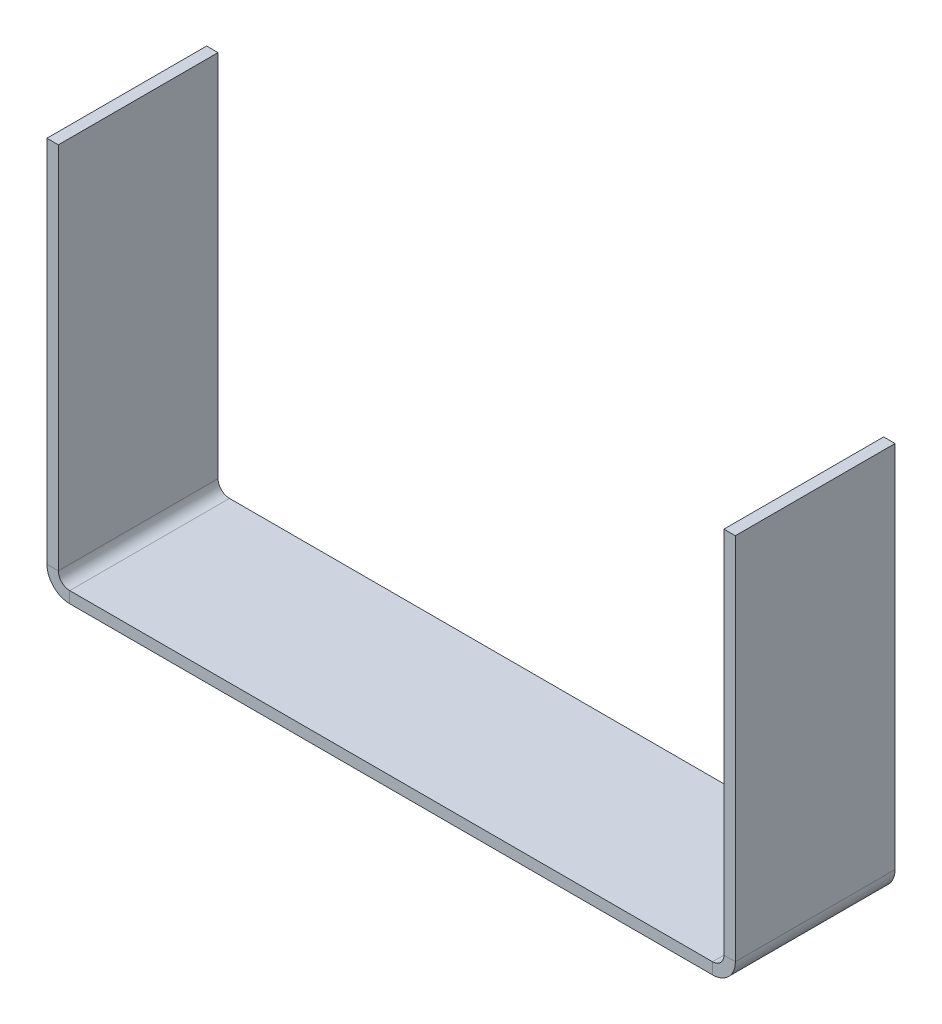
SolidWorks part; units mm, degrees
note: The reader was unsure of these and kept them because the rebuilt part matched: thickness of "Base-Flange1", "Sheet-Metal34"; bend radius of "Base-Flange1", "BaseBend1", "BaseBend2".
material "Tole inox 304 - Z7CN18.09"
ref_plane "Plan de face" through (0, 0, 0) normal (0, 0, 1) x (1, 0, 0)
ref_plane "Plan de dessus" through (0, 0, 0) normal (0, 1, 0) x (1, 0, 0)
ref_plane "Plan de droite" through (0, 0, 0) normal (1, 0, 0) x (0, 0, -1)
sketch "Sketch1" plane through (0, 0, 0) normal (0, 0, 1) x (1, 0, 0)
  line L0 (-87.5, 0) -> (87.5, 0)
  line L1 (-87.5, 0) -> (-87.5, 100)
  line L2 (87.5, 0) -> (87.5, 100)
  point P3 (0, 0)
  dimension "D1" = 175
  dimension "D2" = 100
base flange "Base-Flange1" sketch "Sketch1" end condition mid plane depth 42 reverse direction no thickness 3 reverse thickness direction no bend radius 3
bend "BaseBend1" bend radius 3 bend angle 90 parameters "D5"=1
bend "BaseBend2" bend radius 3 bend angle 90 parameters "D5"=2
sketch "Bend-Lines1" [suppressed] plane through (0, 0, 0) normal (0, 1, 0) x (1, 0, 0)
sketch "Bounding-Box1" [suppressed] plane through (0, 0, 0) normal (0, 1, 0) x (1, 0, 0)
sheet metal parameters "Sheet-Metal34" thickness 3 parameters "D1"=3
flat pattern "Flat-Pattern34" [suppressed]
sketch "Bend-Lines2" plane through (0, 0, 0) normal (0, 1, 0) x (1, 0, 0)
  line L0 (-75.3562, -21) -> (-75.3562, 21) construction
  line L1 (75.3562, 21) -> (75.3562, -21) construction
  line L2 (-75.3562, -21) -> (-75.3562, 21) construction
  line L3 (75.3562, 21) -> (75.3562, -21) construction
sketch3d "Bounding-Box2" [suppressed]
  line L0 (250.7124, 42, 0) -> (-100.7124, 42, 0) construction
  line L1 (250.7124, 0, 0) -> (-100.7124, 0, 0) construction
  line L2 (250.7124, 42, 0) -> (250.7124, 0, 0) construction
  line L3 (-100.7124, 42, 0) -> (-100.7124, 0, 0) construction
bend of the flat pattern "Flatten-<BaseBend1>1"
bend of the flat pattern "Flatten-<BaseBend2>1"
